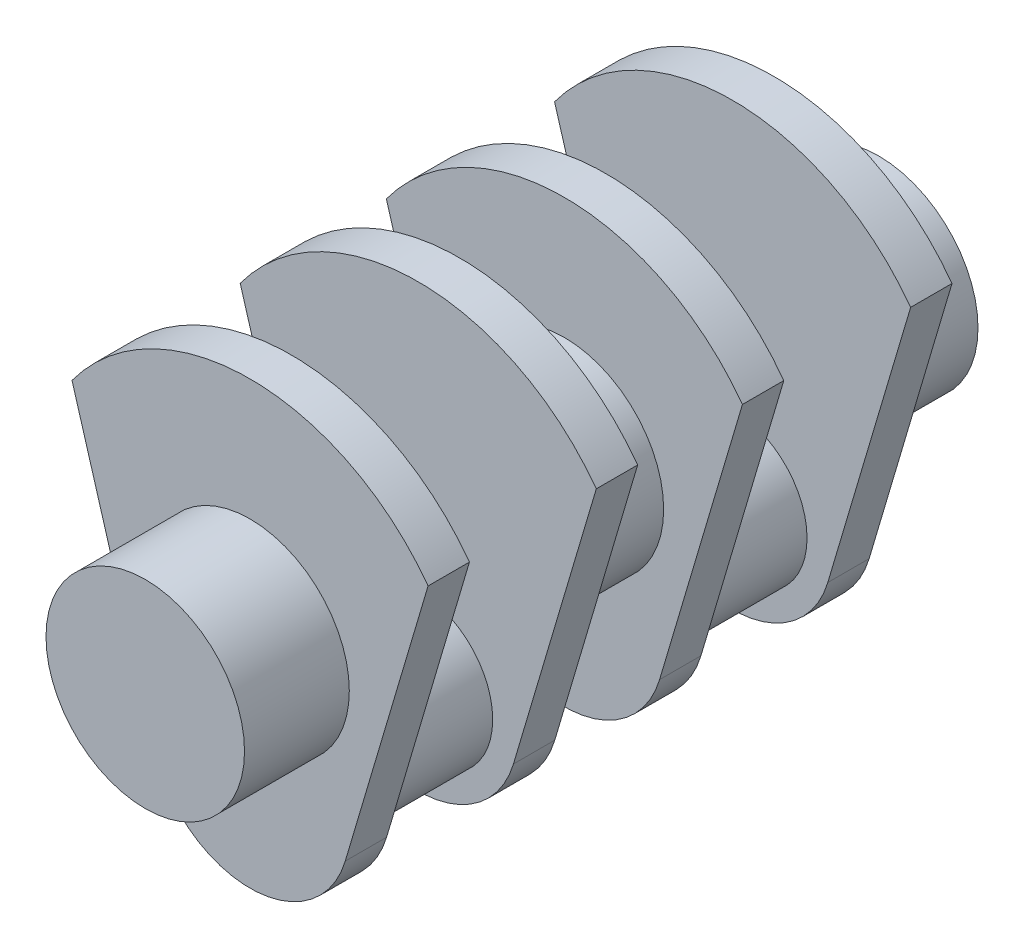
SolidWorks part; units mm, degrees
ref_plane "Front Plane" through (0, 0, 0) normal (0, 0, 1) x (1, 0, 0)
ref_plane "Top Plane" through (0, 0, 0) normal (0, 1, 0) x (1, 0, 0)
ref_plane "Right Plane" through (0, 0, 0) normal (1, 0, 0) x (0, 0, -1)
sketch "Sketch2" plane through (0, 0, 0) normal (0, 0, 1) x (1, 0, 0)
  line L0 (0, 125.44) -> (0, -44) construction
  line L1 (-127.8616, 0) -> (148.2033, 0) construction
  line L2 (64.5699, 47.2306) -> (34.5175, -54.2246)
  line L3 (-64.5699, 47.2306) -> (-34.5175, -54.2246)
  arc A0 (-34.5175, -54.2246) -> (34.5175, -54.2246) centre (0, -44) ccw
  arc A1 (-64.5699, 47.2306) -> (64.5699, 47.2306) centre (0, 0) cw
  dimension "D1" = 72
  dimension "D4" = 80
  dimension "D2" = 44
  dimension "D3" = 0
  dimension "D5" = 33
  dimension "D6" = 16.5
extrude "Boss-Extrude2" add sketch "Sketch2" along normal blind 15 contours A1 L2 A0 L3
sketch "Sketch3" plane through (0, 0, 15) normal (0, 0, 1) x (1, 0, 0)
  circle A0 centre (0, -44) radius 27
  dimension "D1" = 54
extrude "Boss-Extrude3" add sketch "Sketch3" along normal blind 46
sketch "Sketch4" plane through (0, 0, 0) normal (0, 0, -1) x (-1, 0, 0)
  circle A0 centre (0, 0) radius 36
  dimension "D1" = 72
extrude "Boss-Extrude4" add sketch "Sketch4" along normal blind 38
ref_plane "Plane1" through (0, 0, 38) normal (0, 0, 1) x (1, 0, 0)
mirror "Mirror2" about plane through (0, 0, 38) normal (0, 0, 1) of "Boss-Extrude2", "Boss-Extrude3", "Boss-Extrude4"
ref_plane "Plane2" through (0, 0, 95) normal (0, 0, 1) x (1, 0, 0)
mirror "Mirror3" about plane through (0, 0, 95) normal (0, 0, 1) of "Mirror2"
